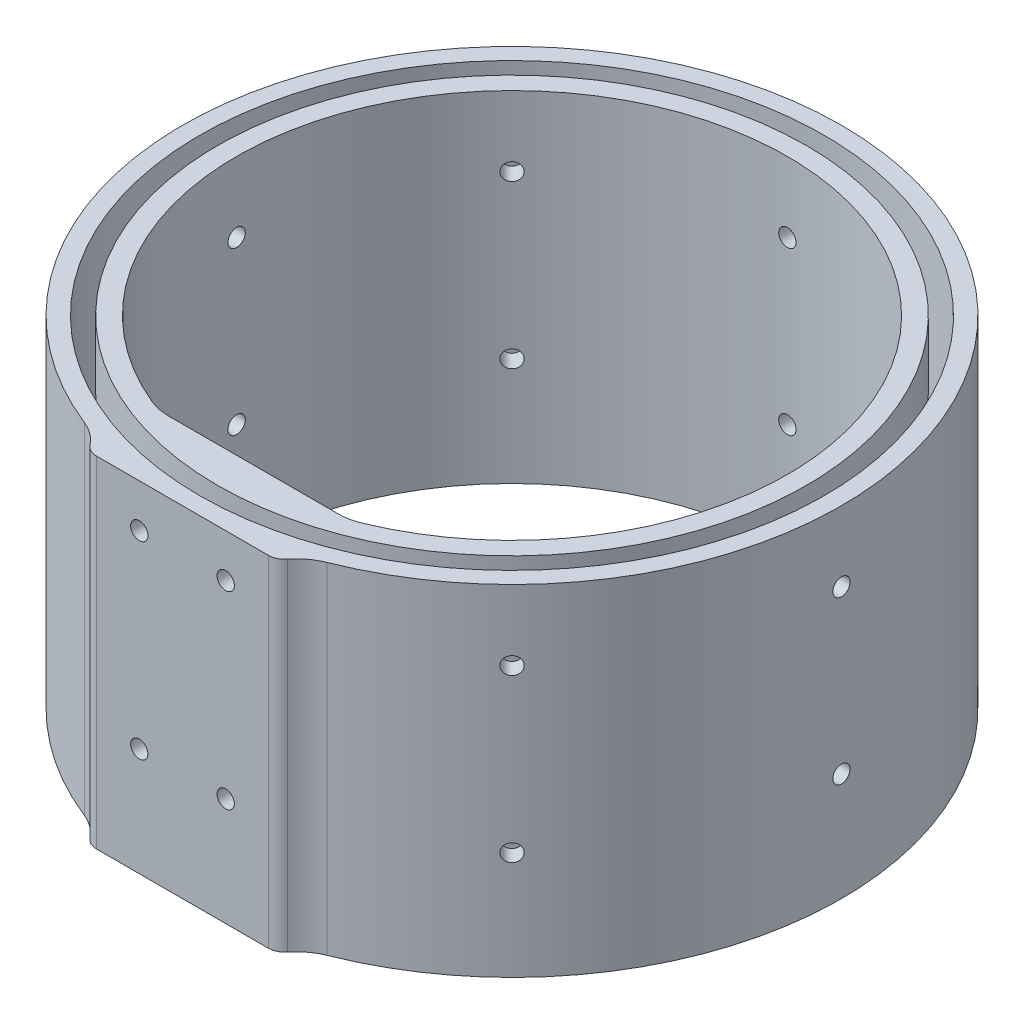
SolidWorks part; units mm, degrees
ref_plane "Front Plane" through (0, 0, 0) normal (0, 0, 1) x (1, 0, 0)
ref_plane "Top Plane" through (0, 0, 0) normal (0, 1, 0) x (1, 0, 0)
ref_plane "Right Plane" through (0, 0, 0) normal (1, 0, 0) x (0, 0, -1)
sketch "Sketch1" plane through (0, 0, 0) normal (0, 1, 0) x (1, 0, 0)
  circle A0 centre (0, 0) radius 56 construction
  circle A1 centre (0, 0) radius 51
  circle A2 centre (0, 0) radius 61
  dimension "D1" = 112
  dimension "D2" = 5
  dimension "D3" = 5
extrude "Boss-Extrude1" add sketch "Sketch1" along normal blind 3 contours A0 A1 region at (-59.2747, 0, 0)
sketch "Sketch3" plane through (0, 3, 0) normal (0, 1, 0) x (1, 0, 0)
  line L1 (-17.5, -47.9035) -> (17.5, -47.9035)
  line L3 (-17.5, -61) -> (17.5, -61)
  line L5 (-17.5, -58.4359) -> (-17.5, -61)
  line L6 (17.5, -58.4359) -> (17.5, -61)
  circle A0 centre (0, 0) radius 56 construction
  circle A1 centre (0, 0) radius 54.5
  circle A2 centre (0, 0) radius 57.8
  circle A3 centre (0, 0) radius 61
  circle A5 centre (0, 0) radius 61 construction
  circle A6 centre (0, 0) radius 51 construction
  point P6 (0, 0)
  point P13 (0, -47.9035)
  point P15 (0, 0)
  point P17 (0, 0)
  point P20 (0, 0)
  circle M2 centre (0, 0) radius 51
  circle M4 centre (0, 0) radius 61
  dimension "D1" = 112
  dimension "D2" = 1.5
  dimension "D3" = 1.8
  dimension "D4" = 35
extrude "Boss-Extrude2" add sketch "Sketch3" along normal blind 60 and the other way up to surface contours A1 M2 | A3 A2 | L1 M2 | L6 L3 M4 | L5 L3 M4 region at (0, 3, 49.1454) region at (-13.1436, 3, 60.2336) region at (13.1436, 3, 60.2336) region at (-8.5933, 3, 58.6484) region at (-52.9585, 3, 0) other way up to face at (0, 0, 51)
sketch "Sketch5" plane through (0, 0, 61) normal (0, 0, 1) x (1, 0, 0)
  line L0 (17.5, 0) -> (-17.5, 0) construction
  line L1 (-8, 55) -> (8, 55) construction
  line L2 (-8, 55) -> (-8, 20) construction
  line L3 (-8, 20) -> (8, 20) construction
  line L4 (8, 55) -> (8, 20) construction
  circle A0 centre (-8, 55) radius 1.6
  circle A1 centre (8, 55) radius 1.6
  circle A2 centre (-8, 20) radius 1.6
  circle A3 centre (8, 20) radius 1.6
  point P4 (0, 20)
  dimension "D4" = 3.2
  dimension "D1" = 16
  dimension "D2" = 35
  dimension "D3" = 20
extrude "Cut-Extrude1" cut sketch "Sketch5" against normal up to surface (13.0965 mm away) up to face at (0, 31.5, 47.9035)
ref_plane "Plane1" through (-61, 0, 0) normal (-1, 0, 0) x (0, 0, 1)
sketch "Sketch6" plane through (-61, 0, 0) normal (-1, 0, 0) x (0, 0, 1)
  line L1 (-61, 0) -> (58.4359, 0) construction
  circle A0 centre (0, 20) radius 1.6
  circle A1 centre (0, 50) radius 1.6
  point P2 (0, 0)
  dimension "D1" = 3.2
  dimension "D2" = 20
  dimension "D3" = 30
extrude "Cut-Extrude3" cut sketch "Sketch6" against normal up to surface (10.0251 mm away) up to face at (0, 31.5, -1.5482)
pattern_circular "CirPattern1" count 8 over 360 about axis through (0, 63, 0) along (0, -1, 0) skipping 6 of "Cut-Extrude3"
fillet "Fillet1" radius 10 4 edges at (-17.5, 31.5, 58.4359) (17.5, 31.5, 58.4359) (17.5, 31.5, 47.9035) (-17.5, 31.5, 47.9035)
fillet "Fillet2" radius 3 2 edges at (-17.5, 31.5, 61) (17.5, 31.5, 61)
